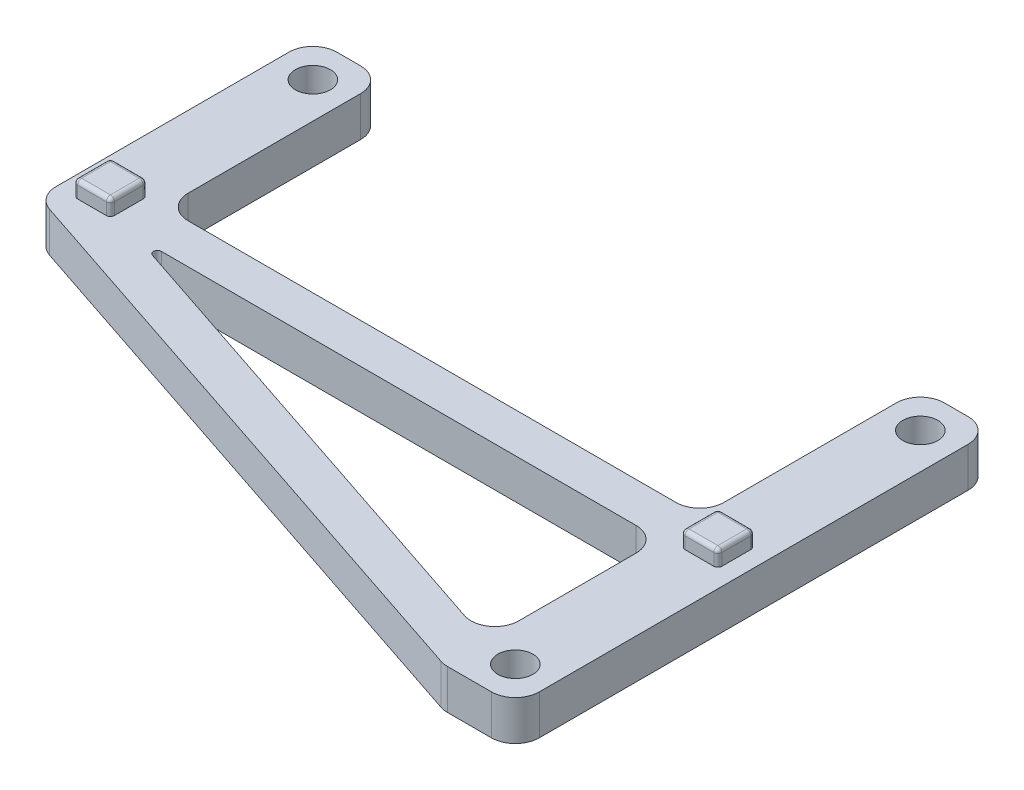
SolidWorks part; units mm, degrees
ref_plane "Front Plane" through (0, 0, 0) normal (0, 0, 1) x (1, 0, 0)
ref_plane "Top Plane" through (0, 0, 0) normal (0, 1, 0) x (1, 0, 0)
ref_plane "Right Plane" through (0, 0, 0) normal (1, 0, 0) x (0, 0, -1)
sketch "Sketch1" plane through (0, 0, 0) normal (0, 1, 0) x (1, 0, 0)
  line L0 (-80.7, 4.5) -> (-71.7, 4.5)
  line L1 (-71.7, 4.5) -> (-71.7, -23.15)
  line L2 (-71.7, -23.15) -> (-4.5, -23.15)
  line L3 (-4.5, -23.15) -> (-4.5, 4.5)
  line L4 (-4.5, 4.5) -> (4.5, 4.5)
  line L5 (4.5, 4.5) -> (4.5, -55.3)
  line L6 (4.5, -55.3) -> (-4.5, -55.3)
  line L7 (-4.5, -55.3) -> (-80.7, -29.9)
  line L8 (-80.7, -29.9) -> (-80.7, 4.5)
  line L12 (-76.2, 4.5) -> (-76.2, -31.4) construction
  line L13 (-78.5114, -27.7114) -> (-73.8886, -27.7114)
  line L14 (-78.5114, -27.7114) -> (-78.5114, -23.0886)
  line L15 (-78.5114, -23.0886) -> (-73.8886, -23.0886)
  line L16 (-73.8886, -27.7114) -> (-73.8886, -23.0886)
  line L17 (-78.5114, -27.7114) -> (-73.8886, -23.0886) construction
  line L18 (-78.5114, -23.0886) -> (-73.8886, -27.7114) construction
  line L19 (-2.3114, -27.7114) -> (2.3114, -27.7114)
  line L20 (-2.3114, -27.7114) -> (-2.3114, -23.0886)
  line L21 (-2.3114, -23.0886) -> (2.3114, -23.0886)
  line L22 (2.3114, -27.7114) -> (2.3114, -23.0886)
  line L23 (-2.3114, -27.7114) -> (2.3114, -23.0886) construction
  line L24 (-2.3114, -23.0886) -> (2.3114, -27.7114) construction
  line L25 (0, 4.5) -> (0, -55.3) construction
  line L26 (-70.1386, -28.15) -> (-4.5, -28.15)
  line L27 (-4.5, -28.15) -> (-4.5, -50.0295)
  line L28 (-4.5, -50.0295) -> (-70.1386, -28.15)
  circle A0 centre (0, 0) radius 2.2
  circle A1 centre (-76.2, 0) radius 2.2
  circle A2 centre (0, -50.8) radius 2.2
  point P16 (-76.2, -25.4)
  point P17 (0, 0)
  point P22 (0, -25.4)
  point P34 (0, -55.3)
  point P36 (0, 0)
  point P37 (0, 0)
  dimension "D1" = 4.4
  dimension "D2" = 4.4
  dimension "D15" = 4.4
  dimension "D3" = 76.2
  dimension "D4" = 9
  dimension "D5" = 4.5
  dimension "D6" = 9
  dimension "D7" = 4.5
  dimension "D8" = 2.25
  dimension "D9" = 5
  dimension "D10" = 4.5
  dimension "D11" = 50.8
  dimension "D12" = 25.4
  dimension "D13" = 25.4
  dimension "D14" = 4.5
  dimension "D16" = 5
  dimension "D17" = 4.6228
  dimension "D18" = 4.6228
extrude "Boss-Extrude1" add sketch "Sketch1" along normal blind 5 contours L13 L16 L15 L14 | L8 L7 L6 L5 L4 L3 L2 L1 L0 A2 A1 A0 L22 L19 L20 L21 L16 L13 L14 L15 L26 | L19 L22 L21 L20 region at (-32.8702, 0, 26.9733) region at (-76.2, 0, 25.4) region at (0, 0, 25.4)
extrude "Boss-Extrude2" add sketch "Sketch1<3>" along normal blind 2 from surface contours L13 L16 L15 L14 | L19 L22 L21 L20 region at (-76.2, 0, 25.4) region at (0, 0, 25.4) starting at face at (0, 5, 53)
sketch "Sketch1<3>" plane through (0, 0, 0) normal (0, 1, 0) x (1, 0, 0) same geometry as "Sketch1"
fillet "Fillet1" radius 3 11 edges at (-4.5, 2.5, -4.5) (4.5, 2.5, -4.5) (4.5, 2.5, 55.3) (-4.5, 2.5, 55.3) (-4.5, 2.5, 50.0295) (-4.5, 2.5, 28.15) (-4.5, 2.5, 23.15) (-80.7, 2.5, 29.9) (-71.7, 2.5, 23.15) (-71.7, 2.5, -4.5) (-80.7, 2.5, -4.5)
fillet "Fillet2" radius 0.508 16 edges at (0, 7, 23.0886) (2.3114, 7, 25.4) (0, 7, 27.7114) (-2.3114, 7, 25.4) (-76.2, 7, 23.0886) (-73.8886, 7, 25.4) (-76.2, 7, 27.7114) (-78.5114, 7, 25.4) (-2.3114, 6, 27.7114) (2.3114, 6, 27.7114) (2.3114, 6, 23.0886) (-2.3114, 6, 23.0886) (-78.5114, 6, 27.7114) (-73.8886, 6, 27.7114) (-73.8886, 6, 23.0886) (-78.5114, 6, 23.0886)
fillet "Fillet3" radius 0.5 1 edges at (-70.1386, 2.5, 28.15)
